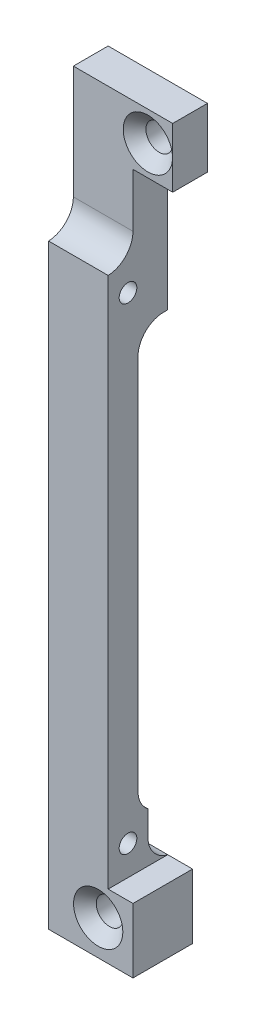
SolidWorks part; units mm, degrees
material "6061-T6 (SS)"
ref_plane "Front Plane" through (0, 0, 0) normal (0, 0, 1) x (1, 0, 0)
ref_plane "Top Plane" through (0, 0, 0) normal (0, 1, 0) x (1, 0, 0)
ref_plane "Right Plane" through (0, 0, 0) normal (1, 0, 0) x (0, 0, -1)
sketch "Sketch1" plane through (0, 0, 0) normal (0, 0, 1) x (1, 0, 0)
  line L0 (0, -93.98) -> (0, -7.62)
  line L1 (0, -55) -> (0, 55) construction
  line L2 (0, -93.98) -> (7.62, -93.98)
  line L3 (7.62, -93.98) -> (7.62, -7.62)
  line L4 (7.62, -7.62) -> (12.7, -7.62)
  line L5 (12.7, -7.62) -> (12.7, 0)
  line L6 (55, 0) -> (-55, 0) construction
  line L7 (-5.08, 0) -> (12.7, 0)
  line L8 (0, -7.62) -> (-5.08, -7.62)
  line L9 (-5.08, -7.62) -> (-5.08, 0)
  dimension "D1" = 7.62
  dimension "D3" = 7.62
  dimension "D4" = 5.08
extrude "Boss-Extrude1" add sketch "Sketch1" along normal blind 7.62
sketch "Sketch11" plane through (0, 0, 7.62) normal (0, 0, 1) x (1, 0, 0)
  line L0 (12.7, -7.62) -> (12.7, 0) construction
  line L1 (-5.08, 0) -> (12.7, 0)
  line L2 (-5.08, 0) -> (-5.08, -17.78)
  line L3 (-5.08, -17.78) -> (12.7, -17.78)
  line L4 (12.7, 0) -> (12.7, -17.78)
  dimension "D1" = 17.78
extrude "Cut-Extrude1" cut sketch "Sketch11" against normal blind 3.175
sketch "Sketch12" plane through (7.62, 0, 0) normal (1, 0, 0) x (0, 0, -1)
  line L0 (0, -93.98) -> (0, -7.62) construction
  line L1 (0, -25.4) -> (-3.81, -25.4)
  line L2 (0, -25.4) -> (0, -85.725)
  line L3 (0, -85.725) -> (-3.81, -85.725)
  line L4 (-3.81, -25.4) -> (-3.81, -85.725)
  line L6 (-7.62, -93.98) -> (0, -93.98) construction
  line L7 (-4.445, -17.78) -> (-7.62, -17.78) construction
  dimension "D1" = 3.81
  dimension "D2" = 7.62
  dimension "D3" = 8.255
extrude "Cut-Extrude2" cut sketch "Sketch12" against normal through all
ref_plane "Plane1" through (3.81, 0, 0) normal (1, 0, 0) x (0, 0, -1)
sketch "Sketch14" plane through (7.62, 0, 0) normal (1, 0, 0) x (0, 0, -1)
  line L1 (0, -85.725) -> (-7.62, -85.725)
  line L2 (0, -85.725) -> (0, -93.98)
  line L3 (0, -93.98) -> (-7.62, -93.98)
  line L4 (-7.62, -85.725) -> (-7.62, -93.98)
extrude "Boss-Extrude3" add sketch "Sketch14" along normal blind 3.175
mirror "Mirror1" about plane through (3.81, 0, 0) normal (1, 0, 0) of "Boss-Extrude3"
sketch "Sketch13" plane through (0, 0, 4.445) normal (0, 0, 1) x (1, 0, 0)
  line L2 (9.525, -3.81) -> (3.81, -3.81) construction
  line L3 (3.81, -3.81) -> (3.81, 0) construction
  line L4 (12.7, 0) -> (-5.08, 0) construction
  line L5 (3.81, -3.81) -> (-1.905, -3.81) construction
  dimension "D1" = 5.715
sketch "Sketch15" plane through (0, 0, 7.62) normal (0, 0, 1) x (1, 0, 0)
  line L0 (9.525, -3.81) -> (3.81, -3.81) construction
  line L2 (3.81, -89.535) -> (1.27, -89.535) construction
  line L4 (3.81, -93.98) -> (3.81, -89.535) construction
  line L5 (-3.175, -93.98) -> (10.795, -93.98) construction
  line L6 (3.81, -89.535) -> (6.35, -89.535) construction
  dimension "D1" = 85.725
  dimension "D2" = 3.175
sketch "Sketch24" plane through (0, 0, 3.81) normal (0, 0, -1) x (-1, 0, 0)
  line L1 (-7.62, -85.725) -> (0, -85.725)
  line L2 (-7.62, -85.725) -> (-7.62, -79.375)
  line L3 (-7.62, -79.375) -> (0, -79.375)
  line L4 (0, -85.725) -> (0, -79.375)
  line L5 (0, -25.4) -> (0, -85.725) construction
  dimension "D1" = 6.35
extrude "Boss-Extrude4" add sketch "Sketch24" along normal blind 1.27
hole_wizard "CSK for M3 Flat Head Machine Screw2" positions "Sketch17" profile "Sketch16" countersink size "M3" standard "Ansi Metric" end condition through all
sketch "Sketch17" plane through (0, 0, 7.62) normal (0, 0, 1) x (1, 0, 0)
  point P1 (6.35, -89.535)
sketch "Sketch16" plane through (6.35, -89.535, 7.62) normal (1, 0, 0) x (0, -1, 0)
  line L0 (0, 0) -> (0, 7.62)
  line L1 (0, 7.62) -> (1.7, 7.62)
  line L2 (1.7, 7.62) -> (1.7, 1.45)
  line L3 (1.7, 1.45) -> (3.15, 0)
  line L5 (3.15, 0) -> (0, 0)
  line L6 (-1.7, 1.45) -> (-3.15, 0) construction
  line L11 (0, -6.35) -> (0, 107.95) construction
  dimension "Thru Hole Dia." = 3.4
  dimension "Thru Hole Depth" = 7.62
  dimension "Near C'Sink Dia." = 6.3
  dimension "Near C'Sink Angle" = 90
hole_wizard "CSK for M3 Flat Head Machine Screw3" positions "Sketch19" profile "Sketch18" countersink size "M3" standard "Ansi Metric" end condition through all
sketch "Sketch19" plane through (0, 0, 4.445) normal (0, 0, 1) x (1, 0, 0)
  point P1 (9.525, -3.81)
sketch "Sketch18" plane through (9.525, -3.81, 4.445) normal (1, 0, 0) x (0, -1, 0)
  line L0 (0, 0) -> (0, 4.445)
  line L1 (0, 4.445) -> (1.7, 4.445)
  line L2 (1.7, 4.445) -> (1.7, 1.45)
  line L3 (1.7, 1.45) -> (3.15, 0)
  line L5 (3.15, 0) -> (0, 0)
  line L6 (-1.7, 1.45) -> (-3.15, 0) construction
  line L11 (0, -6.35) -> (0, 107.95) construction
  dimension "Thru Hole Dia." = 3.4
  dimension "Thru Hole Depth" = 4.445
  dimension "Near C'Sink Dia." = 6.3
  dimension "Near C'Sink Angle" = 90
sketch "Sketch20" plane through (7.62, 0, 0) normal (1, 0, 0) x (0, 0, -1)
  line L0 (-7.62, -20.9677) -> (-5.08, -20.9677) construction
  line L1 (-7.62, -85.725) -> (-7.62, -17.78) construction
  line L2 (-7.62, -81.9277) -> (-5.08, -81.9277) construction
  line L3 (-5.08, -20.9677) -> (-5.08, -81.9277) construction
  dimension "D1" = 17.1577
  dimension "D2" = 2.54
  dimension "D3" = 60.96
hole_wizard "#4-40 Tapped Hole2" positions "Sketch22" profile "Sketch21" tap size "#4-40" standard "Ansi Inch"
sketch "Sketch22" plane through (7.62, 0, 0) normal (1, 0, 0) x (0, 0, -1)
  point P1 (-5.08, -20.9677)
  point P6 (-5.08, -81.9277)
sketch "Sketch21" plane through (7.62, -20.9677, 5.08) normal (0, 1, 0) x (0, 0, -1)
  line L0 (0, 0) -> (0, 9.5438)
  line L1 (0, 9.5438) -> (1.1303, 8.8646)
  line L2 (1.1303, 8.8646) -> (1.1303, 0)
  line L5 (1.1303, 0) -> (0, 0)
  line L10 (0, 9.5438) -> (-1.1303, 8.8646) construction
  line L11 (0, -6.35) -> (0, 107.95) construction
  dimension "Tap Drill Dia." = 2.2606
  dimension "Tap Drill Depth" = 8.8646
  dimension "Drill Angle" = 118
cosmetic thread "Hole Thread2" parameters "D1"=5.6896, "D2"=2.8448
cosmetic thread "Hole Thread3" parameters "D1"=5.6896, "D2"=2.8448
sketch "Sketch27" plane through (0, 0, 0) normal (0, 0, -1) x (-1, 0, 0)
  line L0 (3.175, -93.98) -> (-10.795, -93.98) construction
  line L1 (5.08, 0) -> (0, 0)
  line L2 (5.08, 0) -> (5.08, -93.98)
  line L3 (5.08, -93.98) -> (0, -93.98)
  line L4 (0, 0) -> (0, -93.98)
extrude "Cut-Extrude3" cut sketch "Sketch27" against normal through all
fillet "Fillet1" radius 3.302 4 edges at (3.81, -85.725, 2.54) (3.81, -79.375, 3.81) (3.81, -17.78, 4.445) (3.81, -25.4, 3.81)
sketch "Sketch28" plane through (0, -93.98, 0) normal (0, -1, 0) x (1, 0, 0)
  line L0 (10.795, 7.62) -> (36.195, 7.62) construction
  dimension "D1" = 25.4
